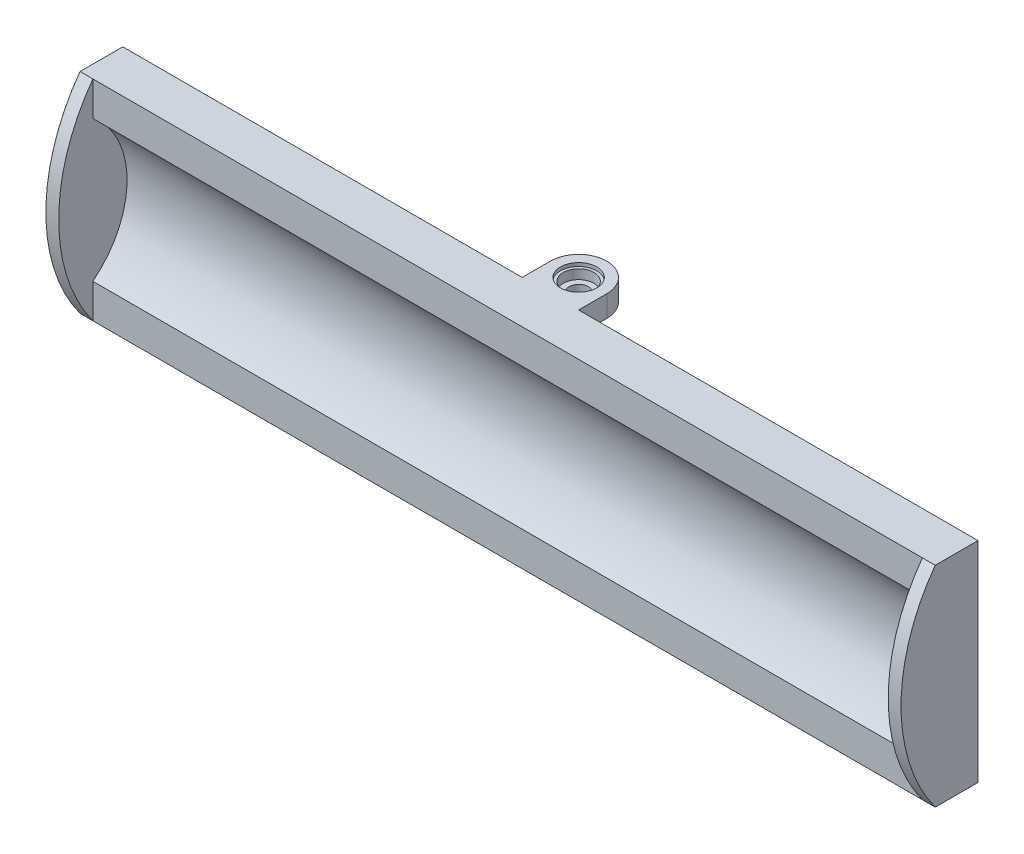
SolidWorks part; units mm, degrees
ref_plane "Front Plane" through (0, 0, 0) normal (1, 0, 0) x (0, 1, 0)
ref_plane "Top Plane" through (0, 0, 0) normal (0, 0, 1) x (0, 1, 0)
ref_plane "Right Plane" through (0, 0, 0) normal (0, 1, 0) x (-1, 0, 0)
sketch "Sketch1" plane through (0, 0, 0) normal (1, 0, 0) x (0, 1, 0)
  line L0 (-5.9881, -2) -> (7.7891, -2) construction
  line L1 (-24.5, -5) -> (24.5, -5)
  line L2 (-24.5, -5) -> (-24.5, 5)
  line L3 (-24.5, 5) -> (24.5, 5)
  line L4 (24.5, -5) -> (24.5, 5)
  line L5 (-24.5, -5) -> (24.5, 5) construction
  line L6 (-24.5, 5) -> (24.5, -5) construction
  circle A0 centre (0, 18) radius 20 construction
  circle A1 centre (0, 18) radius 21
  point P0 (0, 0)
  dimension "D3" = 40
  dimension "D4" = 3
  dimension "D1" = 49
  dimension "D2" = 10
  dimension "D5" = 1
extrude "Boss-Extrude1" add sketch "Sketch1" along normal mid plane 200 contours A1 L3 L2 L1 L4 region at (0, -23.9999, 0)
ref_plane "Midplane Width" through (0, 0, 0) normal (0, -1, 0) x (-1, 0, 0)
sketch "Sketch3" plane through (0, -24.5, 0) normal (0, -1, 0) x (1, 0, 0)
  line L0 (100, -5) -> (-100, -5) construction
  line L1 (-6.6, -11.6) -> (-6.6, -5)
  line L2 (6.6, -11.6) -> (6.6, -5)
  line L3 (-6.6, -5) -> (6.6, -5)
  circle A0 centre (0, -11.6) radius 3.6
  circle A1 centre (0, -11.6) radius 6.6
  line M4 (-100, -5) -> (100, -5)
  dimension "D1" = 7.2
  dimension "D2" = 3
extrude "Boss-Extrude2" add sketch "Sketch3" against normal blind 5 contours A1 A0 | A1 L1 M4 | A1 L2 L3 region at (-4.5349, -24.5, -7.0651) region at (-5.1258, -24.5, -6.4742) region at (5.1258, -24.5, -6.4742)
sketch "Sketch4" plane through (0, -24.5, 0) normal (0, -1, 0) x (-1, 0, 0)
  circle A0 centre (0, 11.6) radius 4.25
  circle A1 centre (0, 11.6) radius 3.6 construction
  circle A2 centre (0, 11.6) radius 3.6
  dimension "D1" = 8.5
extrude "Cut-Extrude1" cut sketch "Sketch4" against normal blind 0.8
sketch "Sketch5" plane through (0, -19.5, 0) normal (0, 1, 0) x (-1, 0, 0)
  circle A0 centre (0, -11.6) radius 2.25
  circle A1 centre (0, -11.6) radius 3.6 construction
  circle A2 centre (0, -11.6) radius 3.6
  dimension "D1" = 4.5
extrude "Boss-Extrude4" add sketch "Sketch5" against normal blind 2
mirror "Mirror1" about plane through (0, 0, 0) normal (0, -1, 0) of "Boss-Extrude4", "Boss-Extrude2", "Cut-Extrude1"
sketch "Sketch6" plane through (0, 0, 0) normal (0, -1, 0) x (-1, 0, 0)
  line L0 (0, 11.6) -> (92.5, 11.6)
  line L1 (87.25, 11.6) -> (87.25, 5)
  line L2 (6.6, 5) -> (100, 5) construction
  line L3 (97.75, 11.6) -> (97.75, 5)
  line L4 (97.75, 5) -> (87.25, 5)
  circle A0 centre (92.5, 11.6) radius 2.25
  arc A1 (97.75, 11.6) -> (87.25, 11.6) centre (92.5, 11.6) ccw
  circle A2 centre (92.5, 11.6) radius 5.25 construction
  dimension "D2" = 4.5
  dimension "D1" = 92.5
  dimension "D3" = 3
extrude "Boss-Extrude5" add sketch "Sketch6" along normal blind 3 from offset 7 contours L3 A1 A0 L1 L4 region at (-92.5, 0, -16.6917)
mirror "Mirror2" about plane through (0, 0, 0) normal (0, -1, 0) of "Boss-Extrude5"
sketch "Sketch7" plane through (-100, 0, 0) normal (-1, 0, 0) x (0, -1, 0)
  line L0 (0, 13) -> (-33.9955, 13) construction
  line L1 (-16.4924, 5) -> (16.4924, 5)
  line L5 (-16.4924, 5) -> (-24.5, 5)
  line L6 (-24.5, 5) -> (-24.5, -5)
  line L7 (-24.5, -5) -> (24.5, -5)
  line L8 (24.5, -5) -> (24.5, 5)
  line L9 (24.5, 5) -> (16.4924, 5)
  line L10 (-16.4924, 5) -> (-24.5, 5)
  line L11 (-24.5, 5) -> (-24.5, -5)
  line L12 (-24.5, -5) -> (24.5, -5)
  line L13 (24.5, -5) -> (24.5, 5)
  line L14 (24.5, 5) -> (16.4924, 5)
  arc A0 (24.5, 5) -> (-24.5, 5) centre (0, -28.5156) ccw
  arc A1 (-16.4924, 5) -> (16.4924, 5) centre (0, 18) ccw
  arc A2 (-16.4924, 5) -> (16.4924, 5) centre (0, 18) ccw
  arc M9 (16.4924, 5) -> (-16.4924, 5) centre (0, 18) cw
  line M10 (-16.4924, 5) -> (-24.5, 5)
  line M11 (-24.5, 5) -> (-24.5, -5)
  line M12 (-24.5, -5) -> (24.5, -5)
  line M13 (24.5, -5) -> (24.5, 5)
  line M14 (24.5, 5) -> (16.4924, 5)
  dimension "D2" = 8
  dimension "D1" = 0
extrude "Boss-Extrude6" add sketch "Sketch7" against normal blind 3 contours M14 M9 M10 M11 M12 M13 | L1 M9 | A0 L1 M14 M10 region at (-100, 0, 8.228) region at (-100, 0, -3.5001) region at (-100, 0, 1.7412)
mirror "Mirror3" about plane through (0, 0, 0) normal (1, 0, 0) of "Boss-Extrude6"
